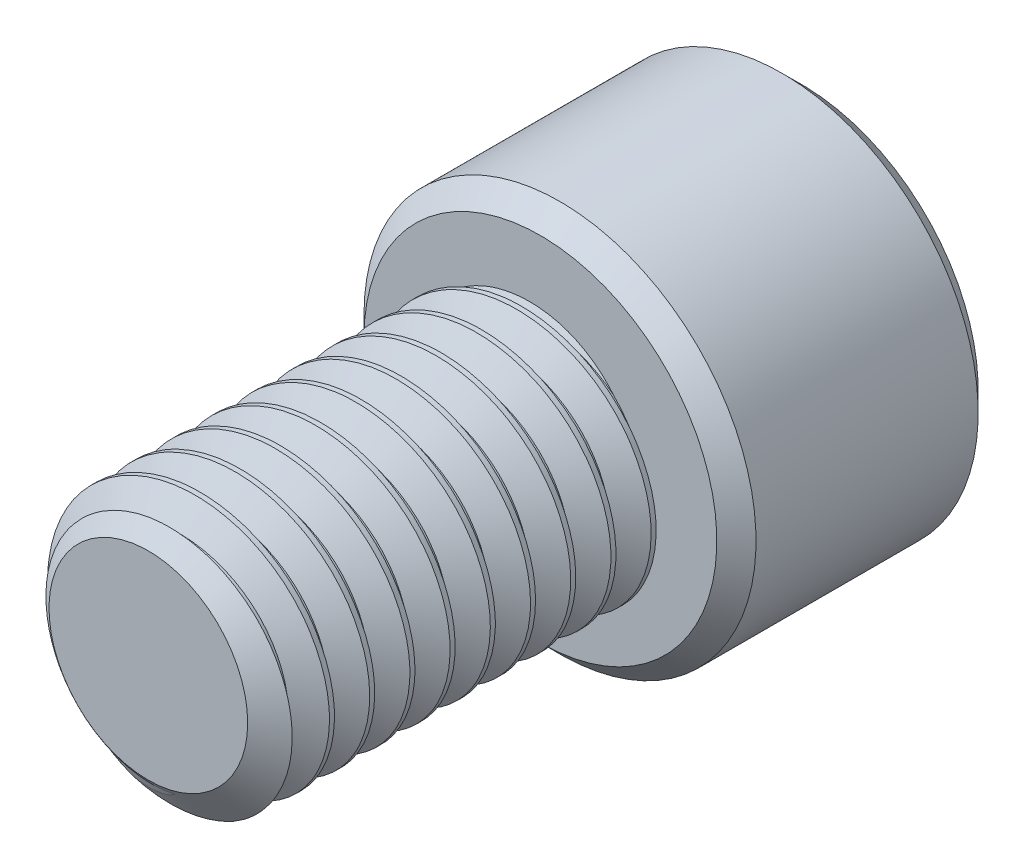
SolidWorks part; units mm, degrees
material "AISI 304"
ref_plane "Front Plane" through (0, 0, 0) normal (0, 0, 1) x (1, 0, 0)
ref_plane "Top Plane" through (0, 0, 0) normal (0, 1, 0) x (1, 0, 0)
ref_plane "Right Plane" through (0, 0, 0) normal (1, 0, 0) x (0, 0, -1)
sketch "Sketch1" plane through (0, 0, 0) normal (0, 0, 1) x (1, 0, 0)
  circle A0 centre (0, 0) radius 6.35
  dimension "OD" = 12.7
extrude "Extrude1" add sketch "Sketch1" against normal blind 19.05
sketch "Sketch2" plane through (0, 0, 0) normal (0, 0, 1) x (1, 0, 0)
  circle A0 centre (0, 0) radius 6.35 construction
  circle A1 centre (0, 0) radius 6.35
curve "Helix/Spiral1" pitch 1.9538 height 21.0038 turns 10.75 parameters "pitch"=1.9538
sketch "Sketch3" plane through (0, 0, 0) normal (1, 0, 0) x (0, 0, -1)
  line L0 (-1.7096, 6.35) -> (-0.9769, 5.0809)
  line L1 (-0.9769, 5.0809) -> (-0.7327, 5.0809)
  line L2 (-0.7327, 5.0809) -> (0, 6.35)
  line L3 (-1.7096, 6.35) -> (0, 6.35)
  line L4 (-0.8548, 6.35) -> (-0.8548, 5.0809) construction
  line L5 (-1.3433, 5.7155) -> (-0.3663, 5.7155) construction
  line L6 (0, 6.35) -> (0, -6.35) construction
  dimension "D1" = 0.2442
  dimension "D2" = 0.9769
  dimension "D3" = 60
sweep "Cut-Sweep1" cut profiles "Sketch3" path "Helix/Spiral1"
sketch "Sketch4" plane through (0, 0, 0) normal (1, 0, 0) x (0, 0, -1)
  line L0 (1.0665, 6.35) -> (0, 4.8269)
  line L1 (0, 4.8269) -> (0, 6.35)
  line L2 (1.0665, 6.35) -> (0, 6.35)
  line L3 (-1.7096, 6.35) -> (0, 6.35) construction
  line L4 (0, 0) -> (7.0209, 0) construction
  dimension "D1" = 55
  dimension "D2" = 0.254
revolve "Cut-Revolve1" cut sketch "Sketch4" angle 360 about L4
sketch "Sketch5" plane through (0, 0, 0) normal (1, 0, 0) x (0, 0, -1)
  line L0 (19.05, -5.9479) -> (19.05, 0) construction
  line L1 (19.05, 6.477) -> (87.4665, 6.477)
  line L2 (19.05, 6.477) -> (19.05, 0)
  line L3 (19.05, 0) -> (87.3125, 0)
  line L4 (87.3125, 6.1468) -> (87.3125, 0)
  line L5 (87.4665, 6.477) -> (87.3125, 6.1468)
  line L6 (0, 0) -> (9.9695, 0) construction
  point P3 (87.3125, 6.477)
  point P10 (87.3125, 6.477)
  dimension "D1" = 0.3302
  dimension "Thread min" = 87.3125
  dimension "D2" = 0.127
  dimension "D3" = 25
revolve "partially thread" [suppressed] add sketch "Sketch5" angle 360 about L6
sketch "Sketch6" plane through (0, 0, -19.05) normal (0, 0, -1) x (-1, 0, 0)
  circle A0 centre (0, 0) radius 9.525
  dimension "head dia" = 19.05
extrude "Extrude2" add sketch "Sketch6" along normal blind 12.7
sketch "Sketch7" plane through (0, 0, -31.75) normal (0, 0, -1) x (-1, 0, 0)
  line L1 (0, 5.4993) -> (-4.7625, 2.7496)
  line L2 (-4.7625, 2.7496) -> (-4.7625, -2.7496)
  line L3 (-4.7625, -2.7496) -> (0, -5.4993)
  line L4 (0, -5.4993) -> (4.7625, -2.7496)
  line L5 (4.7625, -2.7496) -> (4.7625, 2.7496)
  line L6 (4.7625, 2.7496) -> (0, 5.4993)
  circle A0 centre (0, 0) radius 4.7625 construction
  dimension "hex dia" = 9.525
extrude "Cut-Extrude1" cut sketch "Sketch7" against normal blind 7.1438
sketch "Sketch8" plane through (0, 0, -31.75) normal (0, 0, -1) x (-1, 0, 0)
  circle A0 centre (0, 0) radius 5.4993
extrude "Cut-Extrude2" cut sketch "Sketch8" against normal through all draft 45
chamfer "Chamfer1" distance 0.9525 angle 45 2 edges at (-9.525, 0, -31.75) (-9.525, 0, -19.05)
sketch "Sketch9" plane through (0, 0, 0) normal (1, 0, 0) x (0, 0, -1)
  line L0 (0, 6.35) -> (0, -6.35) construction
  line L1 (10.7462, 6.35) -> (10.7462, -6.35) construction
  dimension "D1" = 10.7462
equation "\"D3@Helix/Spiral1\" = \"screw length@Extrude1\"+\"pitch@Helix/Spiral1\""
equation "\"D1@Sketch3\" = \"pitch@Helix/Spiral1\"*.125"
equation "\"D2@Sketch3\" = \"pitch@Helix/Spiral1\"*.5"
equation "\"D1@Cut-Extrude1\" = \"hex dia@Sketch7\"*.75"
equation "\"D1@Chamfer1\" = \"head dia@Sketch6\"*.05"
equation "\"D1@Sketch9\" = \"pitch@Helix/Spiral1\"*5.5"
